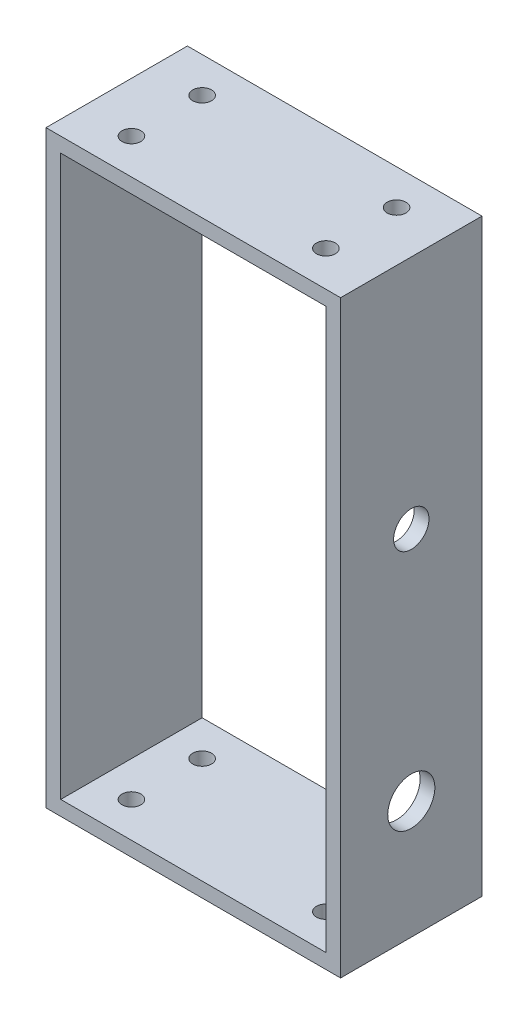
SolidWorks part; units mm, degrees
material "1060 合金"
ref_plane "正面" through (0, 0, 0) normal (0, 0, 1) x (1, 0, 0)
ref_plane "平面" through (0, 0, 0) normal (0, 1, 0) x (1, 0, 0)
ref_plane "右側面" through (0, 0, 0) normal (1, 0, 0) x (0, 0, -1)
sketch "ｽｹｯﾁ1" plane through (0, 0, 0) normal (0, 0, 1) x (1, 0, 0)
  line L0 (-22.5, 47.5) -> (22.5, 47.5)
  line L1 (-25, 50) -> (25, 50)
  line L2 (-25, 50) -> (-25, -50)
  line L3 (-25, -50) -> (25, -50)
  line L4 (25, 50) -> (25, -50)
  line L5 (-25, 50) -> (25, -50) construction
  line L6 (-25, -50) -> (25, 50) construction
  line L7 (22.5, 47.5) -> (22.5, -47.5)
  line L8 (-22.5, -47.5) -> (22.5, -47.5)
  line L9 (-22.5, 47.5) -> (-22.5, -47.5)
  point P0 (0, 0)
  dimension "D2" = 100
  dimension "D3" = 50
  dimension "D1" = 2.5
extrude "ﾎﾞｽ - 押し出し1" add sketch "ｽｹｯﾁ1" along normal blind 24
sketch "ｽｹｯﾁ3" plane through (0, 50, 0) normal (0, 1, 0) x (1, 0, 0)
  line L1 (-25, -24) -> (-25, 0) construction
  line L2 (25, 0) -> (-25, 0) construction
  circle A0 centre (-16.5, -6) radius 1.6
  circle A1 centre (16.5, -6) radius 1.6
  circle A2 centre (16.5, -18) radius 1.6
  circle A3 centre (-16.5, -18) radius 1.6
  dimension "D1" = 33
  dimension "D2" = 8.5
  dimension "D3" = 3.2
  dimension "D4" = 6
  dimension "D6" = 12
  dimension "D5" = 2
extrude "ｶｯﾄ - 押し出し2" cut sketch "ｽｹｯﾁ3" against normal through all and the other way through all
sketch "ｽｹｯﾁ4" plane through (25, 0, 0) normal (1, 0, 0) x (0, 0, -1)
  line L1 (-24, -50) -> (-24, 50) construction
  line L2 (-24, -50) -> (0, -50) construction
  circle A0 centre (-12, 10) radius 3
  circle A1 centre (-12, -30) radius 4
  dimension "D1" = 6
  dimension "D2" = 20
  dimension "D3" = 40
  dimension "D4" = 12
  dimension "D5" = 8
extrude "ｶｯﾄ - 押し出し3" cut sketch "ｽｹｯﾁ4" against normal up to next and the other way through all
